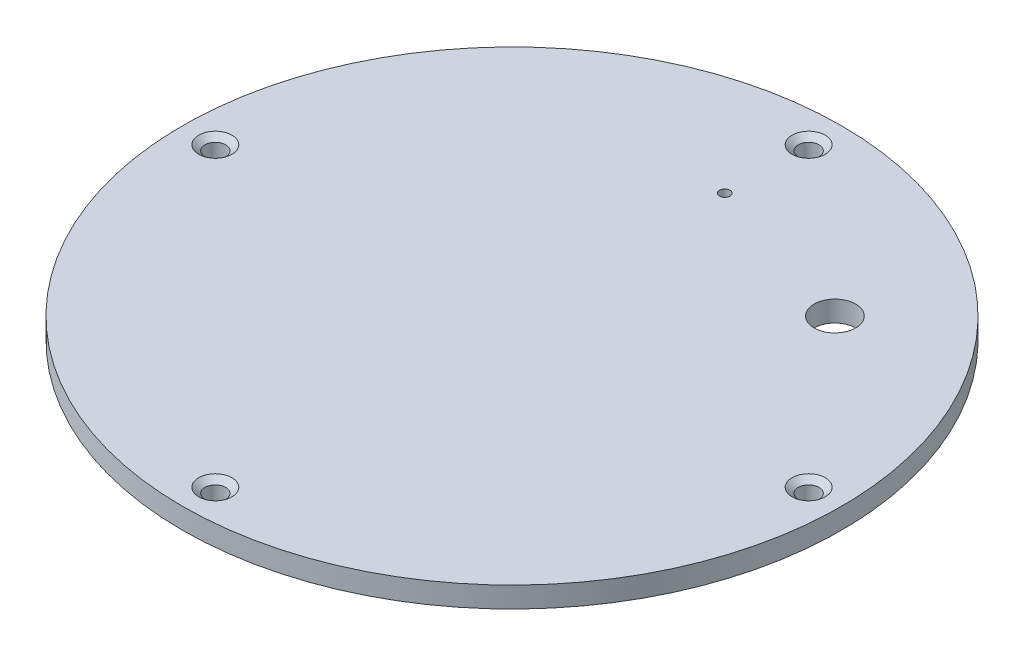
SolidWorks part; units mm, degrees
material "1060 Alloy"
ref_plane "Front Plane" through (0, 0, 0) normal (0, 0, 1) x (1, 0, 0)
ref_plane "Top Plane" through (0, 0, 0) normal (0, 1, 0) x (1, 0, 0)
ref_plane "Right Plane" through (0, 0, 0) normal (1, 0, 0) x (0, 0, -1)
sketch "Sketch1" plane through (0, 0, 0) normal (0, 1, 0) x (1, 0, 0)
  circle A0 centre (0, 0) radius 15.875
  dimension "D1" = 31.75
extrude "Boss-Extrude1" add sketch "Sketch1" along normal blind 1
sketch "Sketch6" plane through (0, 1, 0) normal (0, 1, 0) x (1, 0, 0)
  line L0 (0, 0) -> (13.1331, 13.1331) construction
  line L1 (0, 0) -> (0, 10.25) construction
  circle A0 centre (0, 10.25) radius 0.25
  circle A1 centre (7.7782, 7.7782) radius 1
  dimension "D1" = 10.25
  dimension "D3" = 0.5
  dimension "D4" = 2
  dimension "D2" = 0
  dimension "D5" = 11
  dimension "D6" = 45
extrude "Cut-Extrude1" cut sketch "Sketch6" against normal through all both and the other way through all
hole_wizard "CSK for M2 Flat Head Machine Screw1" positions "Sketch13" profile "Sketch14" countersink size "M2" standard "ANSI Metric" end condition through all
sketch "Sketch13" plane through (0, 1, 0) normal (0, 1, 0) x (1, 0, 0)
  point P0 (0, 14.29)
  point P2 (-14.29, 0)
  point P4 (0, -14.29)
  point P6 (14.29, 0)
  dimension "D1" = 14.29
  dimension "D2" = 14.29
  dimension "D3" = 14.29
  dimension "D4" = 14.29
sketch "Sketch14" plane through (0, 1, -14.29) normal (1, 0, 0) x (0, 0, 1)
  line L0 (0, 0) -> (0, 1)
  line L1 (0, 1) -> (0.5, 1)
  line L2 (0.5, 1) -> (0.5, 0.2517)
  line L3 (0.5, 0.2517) -> (0.8, 0)
  line L5 (0.8, 0) -> (0, 0)
  line L6 (-0.5, 0.2517) -> (-0.8, 0) construction
  line L11 (0, -6.35) -> (0, 107.95) construction
  dimension "Thru Hole Dia." = 1
  dimension "Thru Hole Depth" = 1
  dimension "Near C'Sink Dia." = 1.6
  dimension "Near C'Sink Angle" = 100
